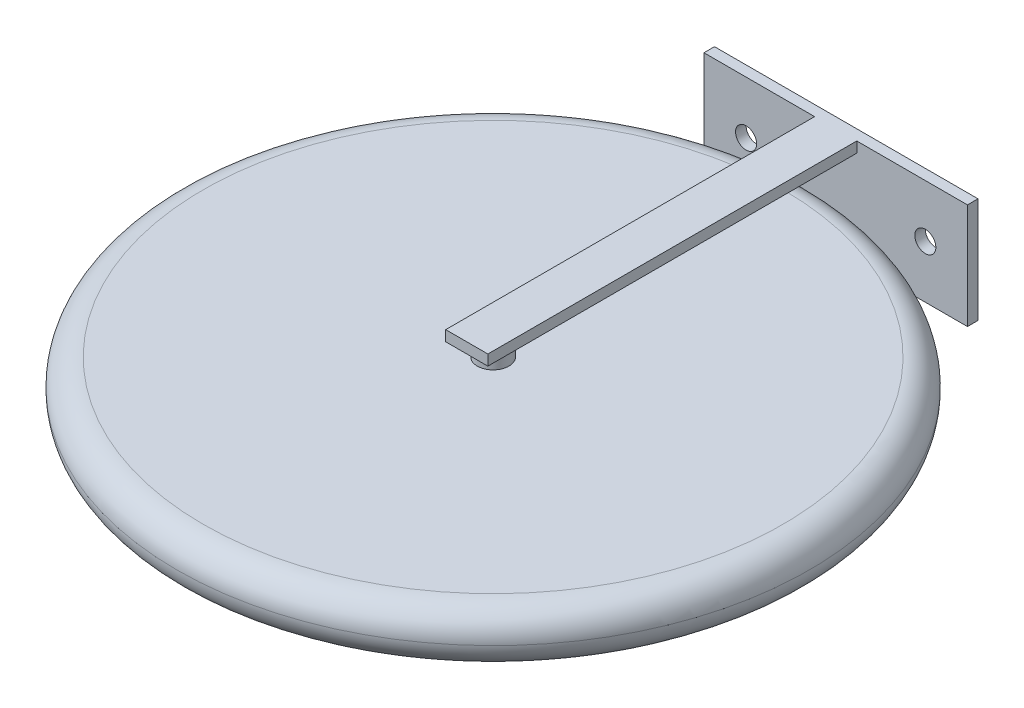
SolidWorks part; units mm, degrees
ref_plane "Front Plane" through (0, 0, 0) normal (0, 0, 1) x (1, 0, 0)
ref_plane "Top Plane" through (0, 0, 0) normal (0, 1, 0) x (1, 0, 0)
ref_plane "Right Plane" through (0, 0, 0) normal (1, 0, 0) x (0, 0, -1)
sketch "Sketch1" plane through (0, 0, 0) normal (0, 1, 0) x (1, 0, 0)
  circle A0 centre (0, 0) radius 60
  circle A1 centre (0, 0) radius 3
  dimension "D1" = 120
  dimension "D2" = 6
extrude "Boss-Extrude1" add sketch "Sketch1" along normal blind 10
sketch "Sketch2" plane through (0, 0, 0) normal (0, 1, 0) x (1, 0, 0)
  circle A0 centre (0, 0) radius 3
  dimension "D1" = 6
extrude "Boss-Extrude2" add sketch "Sketch2" along normal blind 15 and the other way blind 5
sketch "Sketch3" plane through (0, 15, 0) normal (0, 1, 0) x (1, 0, 0)
  line L1 (-4, -5) -> (4, -5)
  line L2 (-4, -5) -> (-4, 65)
  line L3 (-4, 65) -> (4, 65)
  line L4 (4, -5) -> (4, 65)
  line L5 (-4, -5) -> (4, 65) construction
  line L6 (-4, 65) -> (4, -5) construction
  point P0 (0, 30)
  dimension "D1" = 30
  dimension "D2" = 8
  dimension "D3" = 70
  dimension "D4" = 4
extrude "Boss-Extrude3" add sketch "Sketch3" against normal blind 2
extrude "Boss-Extrude4" add sketch "Sketch3<2>" along normal blind 2 from offset 20 offset against normal yes
sketch "Sketch3<2>" plane through (0, 15, 0) normal (0, 1, 0) x (1, 0, 0) same geometry as "Sketch3"
sketch "Sketch4" plane through (0, 0, -65) normal (0, 0, -1) x (-1, 0, 0)
  line L0 (-4, 15) -> (4, 15) construction
  line L1 (-25, -5) -> (25, -5)
  line L2 (-25, -5) -> (-25, 15)
  line L3 (-25, 15) -> (25, 15)
  line L4 (25, -5) -> (25, 15)
  line L5 (-25, -5) -> (25, 15) construction
  line L6 (-25, 15) -> (25, -5) construction
  line L7 (60, 0) -> (60, 10) construction
  line L8 (0, 15) -> (0, 11.9224) construction
  circle A0 centre (-17, 5) radius 2
  circle A1 centre (17, 5) radius 2
  point P0 (0, 5)
  point P7 (0, 15)
  dimension "D5" = 4
  dimension "D7" = 8
  dimension "D8" = 8
  dimension "D1" = 50
  dimension "D2" = 10
  dimension "D3" = 20
  dimension "D4" = 60
  dimension "D6" = 10
  dimension "D9" = 3.0776
extrude "Boss-Extrude5" add sketch "Sketch4" along normal blind 2
fillet "Fillet1" radius 5 2 edges at (0, 10, 60) (0, 0, 60)
